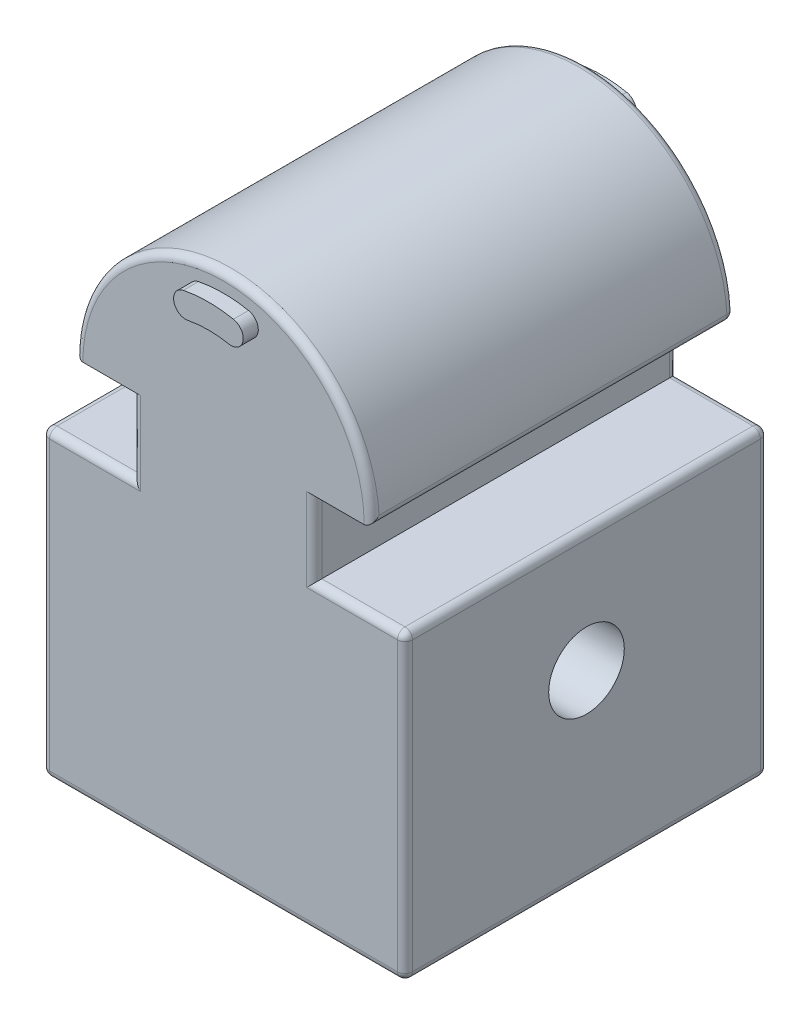
SolidWorks part; units mm, degrees
ref_plane "Front Plane" through (0, 0, 0) normal (0, 0, 1) x (1, 0, 0)
ref_plane "Top Plane" through (0, 0, 0) normal (0, 1, 0) x (1, 0, 0)
ref_plane "Right Plane" through (0, 0, 0) normal (1, 0, 0) x (0, 0, -1)
sketch "Sketch1" plane through (0, 0, 0) normal (0, 0, 1) x (1, 0, 0)
  line L0 (-12.446, 0) -> (12.446, 0)
  line L1 (0, 0) -> (-7.62, 0) construction
  line L2 (0, 9.906) -> (-1.905, 9.906) construction
  line L3 (-7.62, 0) -> (7.62, 0)
  line L7 (0, 9.906) -> (1.905, 9.906) construction
  line L8 (-7.62, -6.35) -> (-15.24, -6.35)
  line L9 (7.62, -6.35) -> (15.24, -6.35)
  line L10 (-7.62, -6.35) -> (-7.62, 0)
  line L12 (-15.24, -6.35) -> (-15.24, -31.75)
  line L15 (7.62, -6.35) -> (7.62, 0)
  line L16 (-15.24, -31.75) -> (15.24, -31.75)
  line L17 (15.24, -31.75) -> (15.24, -6.35)
  arc A0 (12.446, 0) -> (-12.446, 0) centre (0, 0) ccw
  arc A1 (8.636, 0) -> (-8.636, 0) centre (0, 0) ccw
  arc A2 (11.176, 0) -> (-11.176, 0) centre (0, 0) ccw
  arc A3 (11.049, 0) -> (-11.049, 0) centre (0, 0) ccw
  arc A4 (8.89, 0) -> (-8.89, 0) centre (0, 0) ccw
  circle A5 centre (0, 0) radius 11.176 construction
  circle A6 centre (0, 0) radius 11.049 construction
  circle A7 centre (0, 0) radius 8.89 construction
  circle A8 centre (0, 0) radius 8.636 construction
  arc A10 (9.906, 0) -> (-9.906, 0) centre (0, 0) ccw construction
  arc A11 (-1.905, 9.7211) -> (1.905, 9.7211) centre (0, 0) cw construction
  arc A12 (2.1004, 10.7181) -> (-2.1004, 10.7181) centre (0, 0) ccw
  arc A13 (1.7096, 8.7241) -> (-1.7096, 8.7241) centre (0, 0) ccw
  arc A14 (1.7096, 8.7241) -> (2.1004, 10.7181) centre (1.905, 9.7211) ccw
  arc A15 (-2.1004, 10.7181) -> (-1.7096, 8.7241) centre (-1.905, 9.7211) ccw
  arc A16 (-1.905, 9.7211) -> (1.905, 9.7211) centre (0, 0) cw construction
  arc A17 (2.1004, 10.7181) -> (-2.1004, 10.7181) centre (0, 0) ccw
  arc A18 (1.7096, 8.7241) -> (-1.7096, 8.7241) centre (0, 0) ccw
  arc A19 (1.7096, 8.7241) -> (2.1004, 10.7181) centre (1.905, 9.7211) ccw
  arc A20 (-2.1004, 10.7181) -> (-1.7096, 8.7241) centre (-1.905, 9.7211) ccw
  point P31 (0, 9.906)
  point P39 (0, 9.906)
  dimension "D1" = 24.892
  dimension "D2" = 22.352
  dimension "D3" = 17.272
  dimension "D8" = 9.906
  dimension "D11" = 8.89
  dimension "D12" = 10.922
  dimension "D4" = 7.62
  dimension "D7" = 0.254
  dimension "D9" = 1.905
  dimension "D10" = 1.905
  dimension "D14" = 7.62
  dimension "D5" = 7.62
extrude "Main Body Extrude" add sketch "Sketch1" along normal mid plane 30.48 contours L0 | A12 A15 A4 A14 | L0 A0 region at (0, 9.8081, 0) region at (0, -17.2861, 0)
extrude "Slot Extrude" add sketch "Sketch1<4>" along normal mid plane 33.02 contours A12 A15 A4 A14 region at (0, 9.8081, 0)
sketch "Sketch1<4>" plane through (0, 0, 0) normal (0, 0, 1) x (1, 0, 0) same geometry as "Sketch1"
sketch "Sketch2" plane through (0, -31.75, 0) normal (0, -1, 0) x (1, 0, 0)
  line L1 (-9.525, -9.525) -> (9.525, -9.525)
  line L2 (-9.525, -9.525) -> (-9.525, 9.525)
  line L3 (-9.525, 9.525) -> (9.525, 9.525)
  line L4 (9.525, -9.525) -> (9.525, 9.525)
  line L5 (-9.525, -9.525) -> (9.525, 9.525) construction
  line L6 (-9.525, 9.525) -> (9.525, -9.525) construction
  point P0 (0, 0)
  dimension "D1" = 19.05
  dimension "D2" = 19.05
extrude "Foot Connection Cut" cut sketch "Sketch2" against normal blind 22.86
sketch "Sketch4" plane through (-9.525, 0, 0) normal (1, 0, 0) x (0, 0, -1)
  line L0 (0, -8.89) -> (0, -16.51)
  line L5 (-9.525, -31.75) -> (9.525, -31.75)
  line L6 (9.525, -31.75) -> (9.525, -8.89)
  line L7 (9.525, -8.89) -> (-9.525, -8.89)
  line L8 (-9.525, -8.89) -> (-9.525, -31.75)
  line L9 (-9.525, -31.75) -> (9.525, -31.75)
  line L10 (9.525, -31.75) -> (9.525, -8.89)
  line L11 (9.525, -8.89) -> (-9.525, -8.89)
  line L12 (-9.525, -8.89) -> (-9.525, -31.75)
  circle A0 centre (0, -16.51) radius 3.175
  dimension "D3" = 6.35
  dimension "D1" = 7.62
  dimension "D2" = 0
extrude "Pinhole Cut" cut sketch "Sketch4" against normal mid plane 50.8 contours A0 region at (-9.525, -14.3284, -2.1816)
fillet "Fillet1" radius 0.635 24 edges at (11.43, -6.35, 15.24) (12.446, 0, 0) (15.24, -6.35, 0) (7.62, -3.175, 15.24) (-11.43, -6.35, 15.24) (-15.24, -6.35, 0) (-7.62, -3.175, 15.24) (-12.446, 0, 0) (0, 12.446, 15.24) (11.43, -6.35, -15.24) (7.62, -3.175, -15.24) (10.033, 0, -15.24) (-10.033, 0, -15.24) (-7.62, -3.175, -15.24) (-11.43, -6.35, -15.24) (0, 12.446, -15.24) (15.24, -31.75, 0) (-15.24, -31.75, 0) (0, -31.75, 15.24) (0, -31.75, -15.24) (-15.24, -19.05, -15.24) (-15.24, -19.05, 15.24) (15.24, -19.05, 15.24) (15.24, -19.05, -15.24)
equation "\"InnerBaseDiameter\"=0.98"
equation "\"InnerBaseOuterGroove\"= \"InnerBaseDiameter\" - 0.1"
equation "\"InnerHingeInnerCurve\"= 1"
equation "\"InnerHingeOuterCurve\" = \"InnerHingeInnerCurve\" + 0.1"
equation "\"InnerBaseInnerGroove\"= \"InnerBaseOuterGroove\" - 0.2"
equation "\"InnerHingeWidth\"= 1.45"
equation "\"OuterBaseInnerGroove\"= \"OuterBaseOuterGroove\" - 0.25"
equation "\"OuterBaseDiameter\"= ( ( \"InnerHingeOuterCurve\" / 2 ) ^ 2 + ( \"InnerHingeLength\" / 2 ) ^ 2 ) ^ 0.5 * 2"
equation "\"InnerHingeLength\"=1.2"
equation "\"OuterBaseOuterGroove\" = \"OuterBaseDiameter\" - 0.2"
equation "\"D1@Sketch1\"=\"InnerBaseDiameter\""
equation "\"D2@Sketch1\"=\"InnerBaseOuterGroove\""
equation "\"D3@Sketch1\"=\"InnerBaseInnerGroove\""
equation "\"D8@Sketch1\"=\"InnerBaseOuterGroove\"  * 0.25 +\"InnerBaseInnerGroove\" * 0.25"
equation "\"D11@Sketch1\"=\"InnerBaseInnerGroove\" *0.5 +0.01"
equation "\"D12@Sketch1\"=\"InnerBaseOuterGroove\"*0.5 -0.01"
